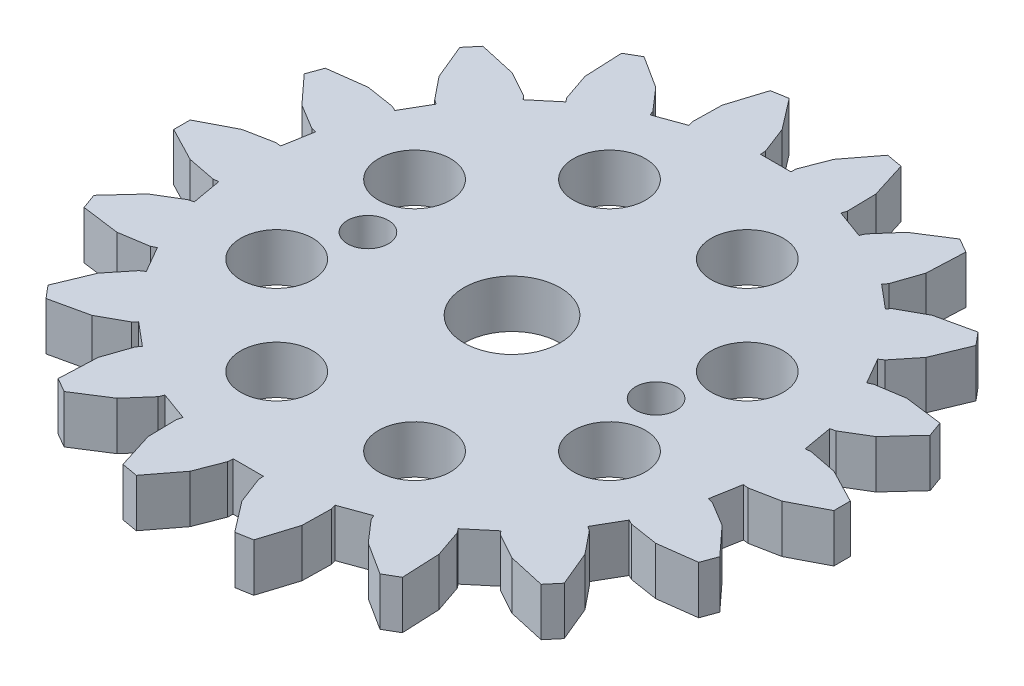
SolidWorks part; units mm, degrees
material "Acrylic (Medium-high impact)"
ref_plane "Front Plane" through (0, 0, 0) normal (0, 0, 1) x (1, 0, 0)
ref_plane "Top Plane" through (0, 0, 0) normal (0, 1, 0) x (1, 0, 0)
ref_plane "Right Plane" through (0, 0, 0) normal (1, 0, 0) x (0, 0, -1)
sketch "Sketch2" plane through (0, 0, 0) normal (0, 1, 0) x (1, 0, 0)
  line L0 (52.5387, 31.8425) -> (52.9668, 31.8929)
  line L1 (52.9668, 31.8929) -> (55.3456, 31.4261)
  line L2 (55.3456, 31.4261) -> (58.181, 29.9538)
  line L3 (58.181, 29.9538) -> (58.181, 28.5845)
  line L4 (58.181, 28.5845) -> (55.3456, 27.1121)
  line L5 (55.3456, 27.1121) -> (52.9668, 26.6454)
  line L6 (52.9668, 26.6454) -> (52.5387, 26.6957)
  line L7 (52.5387, 26.6957) -> (52.1012, 24.2147)
  line L8 (52.1012, 24.2147) -> (52.5208, 24.1156)
  line L9 (52.5208, 24.1156) -> (54.5964, 22.8636)
  line L10 (54.5964, 22.8636) -> (56.7575, 20.51)
  line L11 (56.7575, 20.51) -> (56.289, 19.2232)
  line L12 (56.289, 19.2232) -> (53.1208, 18.8096)
  line L13 (53.1208, 18.8096) -> (50.726, 19.1845)
  line L14 (50.726, 19.1845) -> (50.3409, 19.3783)
  line L15 (50.3409, 19.3783) -> (49.0813, 17.1964)
  line L16 (49.0813, 17.1964) -> (49.4416, 16.9599)
  line L17 (49.4416, 16.9599) -> (50.9638, 15.0733)
  line L18 (50.9638, 15.0733) -> (52.1897, 12.1228)
  line L19 (52.1897, 12.1228) -> (51.3094, 11.0736)
  line L20 (51.3094, 11.0736) -> (48.1906, 11.7686)
  line L21 (48.1906, 11.7686) -> (46.0686, 12.9399)
  line L22 (46.0686, 12.9399) -> (45.7729, 13.2537)
  line L23 (45.7729, 13.2537) -> (43.8429, 11.6343)
  line L24 (43.8429, 11.6343) -> (44.1008, 11.2887)
  line L25 (44.1008, 11.2887) -> (44.8859, 8.9954)
  line L26 (44.8859, 8.9954) -> (45.0286, 5.8036)
  line L27 (45.0286, 5.8036) -> (43.8427, 5.1188)
  line L28 (43.8427, 5.1188) -> (41.1496, 6.8384)
  line L29 (41.1496, 6.8384) -> (39.5561, 8.665)
  line L30 (39.5561, 8.665) -> (39.3857, 9.0611)
  line L31 (39.3857, 9.0611) -> (37.0183, 8.1993)
  line L32 (37.0183, 8.1993) -> (37.1423, 7.7863)
  line L33 (37.1423, 7.7863) -> (37.0956, 5.3628)
  line L34 (37.0956, 5.3628) -> (36.1382, 2.3147)
  line L35 (36.1382, 2.3147) -> (34.7894, 2.0769)
  line L36 (34.7894, 2.0769) -> (32.8471, 4.6136)
  line L37 (32.8471, 4.6136) -> (31.9745, 6.8751)
  line L38 (31.9745, 6.8751) -> (31.9497, 7.3056)
  line L39 (31.9497, 7.3056) -> (29.4305, 7.3056)
  line L40 (29.4305, 7.3056) -> (29.4056, 6.8751)
  line L41 (29.4056, 6.8751) -> (28.5331, 4.6136)
  line L42 (28.5331, 4.6136) -> (26.5908, 2.0769)
  line L43 (26.5908, 2.0769) -> (25.242, 2.3147)
  line L44 (25.242, 2.3147) -> (24.2845, 5.3628)
  line L45 (24.2845, 5.3628) -> (24.2379, 7.7863)
  line L46 (24.2379, 7.7863) -> (24.3618, 8.1993)
  line L47 (24.3618, 8.1993) -> (21.9945, 9.0611)
  line L48 (21.9945, 9.0611) -> (21.8241, 8.665)
  line L49 (21.8241, 8.665) -> (20.2305, 6.8384)
  line L50 (20.2305, 6.8384) -> (17.5375, 5.1188)
  line L51 (17.5375, 5.1188) -> (16.3515, 5.8036)
  line L52 (16.3515, 5.8036) -> (16.4943, 8.9954)
  line L53 (16.4943, 8.9954) -> (17.2794, 11.2887)
  line L54 (17.2794, 11.2887) -> (17.5373, 11.6343)
  line L55 (17.5373, 11.6343) -> (15.6073, 13.2537)
  line L56 (15.6073, 13.2537) -> (15.3116, 12.9399)
  line L57 (15.3116, 12.9399) -> (13.1896, 11.7686)
  line L58 (13.1896, 11.7686) -> (10.0708, 11.0736)
  line L59 (10.0708, 11.0736) -> (9.1904, 12.1228)
  line L60 (9.1904, 12.1228) -> (10.4164, 15.0733)
  line L61 (10.4164, 15.0733) -> (11.9386, 16.9599)
  line L62 (11.9386, 16.9599) -> (12.2989, 17.1964)
  line L63 (12.2989, 17.1964) -> (11.0392, 19.3783)
  line L64 (11.0392, 19.3783) -> (10.6542, 19.1845)
  line L65 (10.6542, 19.1845) -> (8.2594, 18.8096)
  line L66 (8.2594, 18.8096) -> (5.0911, 19.2232)
  line L67 (5.0911, 19.2232) -> (4.6227, 20.51)
  line L68 (4.6227, 20.51) -> (6.7838, 22.8636)
  line L69 (6.7838, 22.8636) -> (8.8594, 24.1156)
  line L70 (8.8594, 24.1156) -> (9.279, 24.2147)
  line L71 (9.279, 24.2147) -> (8.8414, 26.6957)
  line L72 (8.8414, 26.6957) -> (8.4133, 26.6454)
  line L73 (8.4133, 26.6454) -> (6.0345, 27.1121)
  line L74 (6.0345, 27.1121) -> (3.1991, 28.5845)
  line L75 (3.1991, 28.5845) -> (3.1991, 29.9538)
  line L76 (3.1991, 29.9538) -> (6.0345, 31.4261)
  line L77 (6.0345, 31.4261) -> (8.4133, 31.8929)
  line L78 (8.4133, 31.8929) -> (8.8414, 31.8425)
  line L79 (8.8414, 31.8425) -> (9.279, 34.3235)
  line L80 (9.279, 34.3235) -> (8.8594, 34.4226)
  line L81 (8.8594, 34.4226) -> (6.7838, 35.6747)
  line L82 (6.7838, 35.6747) -> (4.6227, 38.0282)
  line L83 (4.6227, 38.0282) -> (5.0911, 39.3151)
  line L84 (5.0911, 39.3151) -> (8.2594, 39.7287)
  line L85 (8.2594, 39.7287) -> (10.6542, 39.3537)
  line L86 (10.6542, 39.3537) -> (11.0392, 39.16)
  line L87 (11.0392, 39.16) -> (12.2989, 41.3418)
  line L88 (12.2989, 41.3418) -> (11.9386, 41.5783)
  line L89 (11.9386, 41.5783) -> (10.4164, 43.4649)
  line L90 (10.4164, 43.4649) -> (9.1904, 46.4154)
  line L91 (9.1904, 46.4154) -> (10.0708, 47.4647)
  line L92 (10.0708, 47.4647) -> (13.1896, 46.7696)
  line L93 (13.1896, 46.7696) -> (15.3116, 45.5984)
  line L94 (15.3116, 45.5984) -> (15.6073, 45.2846)
  line L95 (15.6073, 45.2846) -> (17.5373, 46.904)
  line L96 (17.5373, 46.904) -> (17.2794, 47.2496)
  line L97 (17.2794, 47.2496) -> (16.4943, 49.5428)
  line L98 (16.4943, 49.5428) -> (16.3515, 52.7346)
  line L99 (16.3515, 52.7346) -> (17.5375, 53.4195)
  line L100 (17.5375, 53.4195) -> (20.2305, 51.6998)
  line L101 (20.2305, 51.6998) -> (21.8241, 49.8733)
  line L102 (21.8241, 49.8733) -> (21.9945, 49.4772)
  line L103 (21.9945, 49.4772) -> (24.3618, 50.339)
  line L104 (24.3618, 50.339) -> (24.2379, 50.7519)
  line L105 (24.2379, 50.7519) -> (24.2845, 53.1754)
  line L106 (24.2845, 53.1754) -> (25.242, 56.2236)
  line L107 (25.242, 56.2236) -> (26.5908, 56.4614)
  line L108 (26.5908, 56.4614) -> (28.5331, 53.9247)
  line L109 (28.5331, 53.9247) -> (29.4056, 51.6631)
  line L110 (29.4056, 51.6631) -> (29.4305, 51.2327)
  line L111 (29.4305, 51.2327) -> (31.9497, 51.2327)
  line L112 (31.9497, 51.2327) -> (31.9745, 51.6631)
  line L113 (31.9745, 51.6631) -> (32.8471, 53.9247)
  line L114 (32.8471, 53.9247) -> (34.7894, 56.4614)
  line L115 (34.7894, 56.4614) -> (36.1382, 56.2236)
  line L116 (36.1382, 56.2236) -> (37.0956, 53.1754)
  line L117 (37.0956, 53.1754) -> (37.1423, 50.7519)
  line L118 (37.1423, 50.7519) -> (37.0183, 50.339)
  line L119 (37.0183, 50.339) -> (39.3857, 49.4772)
  line L120 (39.3857, 49.4772) -> (39.5561, 49.8733)
  line L121 (39.5561, 49.8733) -> (41.1496, 51.6998)
  line L122 (41.1496, 51.6998) -> (43.8427, 53.4195)
  line L123 (43.8427, 53.4195) -> (45.0286, 52.7346)
  line L124 (45.0286, 52.7346) -> (44.8859, 49.5428)
  line L125 (44.8859, 49.5428) -> (44.1008, 47.2496)
  line L126 (44.1008, 47.2496) -> (43.8429, 46.904)
  line L127 (43.8429, 46.904) -> (45.7729, 45.2846)
  line L128 (45.7729, 45.2846) -> (46.0686, 45.5984)
  line L129 (46.0686, 45.5984) -> (48.1906, 46.7696)
  line L130 (48.1906, 46.7696) -> (51.3094, 47.4647)
  line L131 (51.3094, 47.4647) -> (52.1897, 46.4154)
  line L132 (52.1897, 46.4154) -> (50.9638, 43.4649)
  line L133 (50.9638, 43.4649) -> (49.4416, 41.5783)
  line L134 (49.4416, 41.5783) -> (49.0813, 41.3418)
  line L135 (49.0813, 41.3418) -> (50.3409, 39.16)
  line L136 (50.3409, 39.16) -> (50.726, 39.3537)
  line L137 (50.726, 39.3537) -> (53.1208, 39.7287)
  line L138 (53.1208, 39.7287) -> (56.289, 39.3151)
  line L139 (56.289, 39.3151) -> (56.7575, 38.0282)
  line L140 (56.7575, 38.0282) -> (54.5964, 35.6747)
  line L141 (54.5964, 35.6747) -> (52.5208, 34.4226)
  line L142 (52.5208, 34.4226) -> (52.1012, 34.3235)
  line L143 (52.1012, 34.3235) -> (52.5387, 31.8425)
  line L144 (30.6901, 51.2327) -> (30.6901, 7.3056) construction
  line L145 (58.181, 29.2691) -> (3.1991, 29.2691) construction
sketch "Sketch3" plane through (0, 0, 0) normal (0, 1, 0) x (1, 0, 0)
  line L0 (30.6901, 51.2327) -> (30.6901, 7.3056) construction
  line L1 (18.6901, 29.2691) -> (42.6901, 29.2691) construction
  line L2 (58.181, 29.2691) -> (3.1991, 29.2691) construction
  line L3 (30.6901, 32.1459) -> (30.6901, 5.7347) construction
  circle A0 centre (30.6901, 29.2691) radius 4
  circle A1 centre (18.6901, 29.2691) radius 1.7
  circle A2 centre (42.6901, 29.2691) radius 1.7
  point P11 (30.6901, 29.2691)
  dimension "D1" = 8
  dimension "D2" = 3.4
  dimension "D3" = 12
extrude "Boss-Extrude1" add sketch "Sketch2" along normal blind 4
extrude "Cut-Extrude1" cut sketch "Sketch3" along normal up to next
sketch "Sketch4" plane through (0, 0, 0) normal (0, 1, 0) x (1, 0, 0)
  line L0 (30.6901, 29.2691) -> (3.1991, 29.2691) construction
  line L1 (3.1991, 29.9538) -> (3.1991, 28.5845) construction
  line L2 (30.6901, 29.2691) -> (0.7129, 41.6861) construction
  circle A0 centre (16.8319, 35.0094) radius 3
  point P0 (30.6901, 29.2691)
  dimension "D3" = 6
  dimension "D1" = 22.5
  dimension "D2" = 15
extrude "Cut-Extrude2" cut sketch "Sketch4" along normal up to next
pattern_circular "CirPattern1" count 8 over 360 about axis through (30.6901, 4, -29.2691) along (0, -1, 0) of "Cut-Extrude2"
